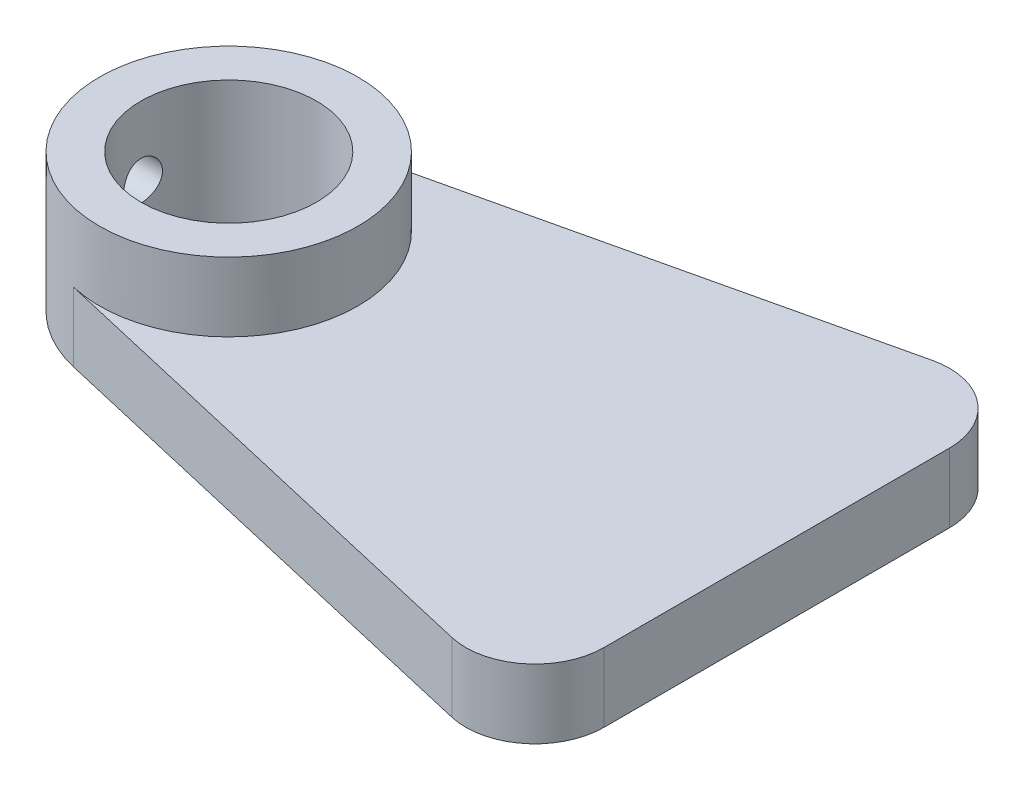
SolidWorks part; units mm, degrees
ref_plane "Front Plane" through (0, 0, 0) normal (0, 0, 1) x (1, 0, 0)
ref_plane "Top Plane" through (0, 0, 0) normal (0, 1, 0) x (1, 0, 0)
ref_plane "Right Plane" through (0, 0, 0) normal (1, 0, 0) x (0, 0, -1)
sketch "Sketch1" plane through (0, 0, 0) normal (0, 1, 0) x (1, 0, 0)
  line L0 (0, 0) -> (34.65, -12.5) construction
  line L1 (34.65, -12.5) -> (34.65, 12.5) construction
  line L2 (34.65, 12.5) -> (0, 0) construction
  line L3 (-2.112, 9.1083) -> (33.5206, 17.3708)
  line L4 (39.65, 12.5) -> (39.65, -12.5)
  line L5 (0, 0) -> (39.65, 0) construction
  line L6 (-2.112, -9.1083) -> (33.5206, -17.3708)
  circle A0 centre (0, 0) radius 6.35
  circle A1 centre (34.65, 12.5) radius 5
  circle A2 centre (34.65, -12.5) radius 5
  circle A3 centre (0, 0) radius 9.35
  dimension "D1" = 12.7
  dimension "D2" = 3
  dimension "D5" = 10
  dimension "D3" = 34.65
  dimension "D4" = 25
extrude "Boss-Extrude1" add sketch "Sketch1" along normal blind 5 contours A3 A0 | A3 L6 A2 L4 A1 L3 | A1 | A2 region at (22.1849, 0, 0) region at (5.6525, 0, -7.1131) region at (34.65, 0, -12.5) region at (34.65, 0, 12.5)
extrude "Boss-Extrude2" add sketch "Sketch1<3>" along normal blind 10 contours A3 A0 region at (5.6525, 0, -7.1131)
sketch "Sketch1<3>" plane through (0, 0, 0) normal (0, 1, 0) x (1, 0, 0) same geometry as "Sketch1"
sketch "Sketch2" plane through (0, 0, 0) normal (1, 0, 0) x (0, 0, -1)
  line L0 (12.5, 5) -> (-12.5, 5) construction
  circle A0 centre (0, 5) radius 1.4
  dimension "D1" = 2.8
extrude "Cut-Extrude1" cut sketch "Sketch2" against normal through all
equation "\"m3 hole\"= 3.2"
equation "\"m4 hole\"= 4.2"
equation "\"m5 hole\"= 5.2"
equation "\"m6 hole\"= 6.2"
equation "\"m8 hole\"= 8.2"
equation "\"m3 tapped\"= 2.5"
equation "\"m4 tapped\"= 3.3"
equation "\"m5 tapped\"= 4.2"
equation "\"m6 tapped\"= 5"
equation "\"m8 tapped\"= 6.8"
